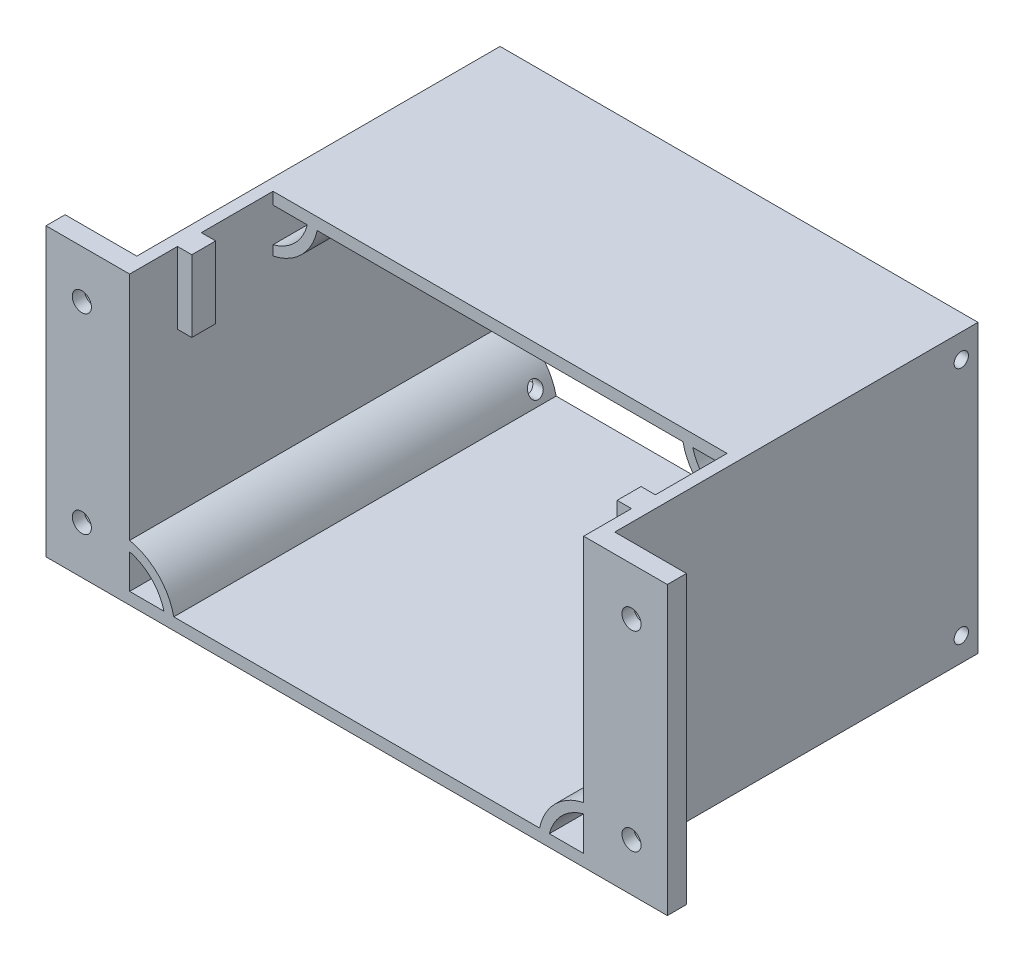
SolidWorks part; units mm, degrees
ref_plane "Front Plane" through (0, 0, 0) normal (0, 0, 1) x (1, 0, 0)
ref_plane "Top Plane" through (0, 0, 0) normal (0, 1, 0) x (1, 0, 0)
ref_plane "Right Plane" through (0, 0, 0) normal (1, 0, 0) x (0, 0, -1)
sketch "Sketch1" plane through (0, 0, 0) normal (0, 0, 1) x (1, 0, 0)
  line L1 (-40.2483, 30.9603) -> (59.7517, 30.9603)
  line L2 (-40.2483, 30.9603) -> (-40.2483, -29.0397)
  line L3 (-40.2483, -29.0397) -> (59.7517, -29.0397)
  line L4 (59.7517, 30.9603) -> (59.7517, -29.0397)
  line L5 (-37.7483, 28.4603) -> (57.2517, 28.4603)
  line L6 (-37.7483, 28.4603) -> (-37.7483, -26.5397)
  line L7 (-37.7483, -26.5397) -> (57.2517, -26.5397)
  line L8 (57.2517, 28.4603) -> (57.2517, -26.5397)
  arc A1 (-37.7483, 19.2236) -> (-28.5116, 28.4603) centre (-40.2483, 30.9603) ccw
  arc A2 (-37.7483, 21.2778) -> (-30.5659, 28.4603) centre (-40.2483, 30.9603) ccw
  arc A3 (48.015, 28.4603) -> (57.2517, 19.2236) centre (59.7517, 30.9603) ccw
  arc A4 (50.0692, 28.4603) -> (57.2517, 21.2778) centre (59.7517, 30.9603) ccw
  arc A5 (-28.5116, -26.5397) -> (-37.7483, -17.303) centre (-40.2483, -29.0397) ccw
  arc A6 (-30.5659, -26.5397) -> (-37.7483, -19.3573) centre (-40.2483, -29.0397) ccw
  arc A7 (57.2517, -17.303) -> (48.015, -26.5397) centre (59.7517, -29.0397) ccw
  arc A8 (57.2517, -19.3573) -> (50.0692, -26.5397) centre (59.7517, -29.0397) ccw
  dimension "D3" = 2.5
  dimension "D1" = 100
  dimension "D2" = 60
  dimension "D4" = 2.5
  dimension "D5" = 2.5
  dimension "D6" = 2.5
extrude "Boss-Extrude1" add sketch "Sketch1" along normal blind 150 contours L4 L1 L2 L3 L5 L8 L7 L6 | A2 L6 A1 L5 | A4 L5 A3 L8 | A8 L8 A7 L7 | A6 L7 A5 L6 region at (9.7517, 29.7941, 0) region at (-32.8375, 23.5494, 0) region at (52.3408, 23.5494, 0) region at (-32.8375, -21.6289, 0) region at (52.3408, -21.6289, 0)
sketch "Sketch2" plane through (0, 30.9603, 0) normal (0, 1, 0) x (1, 0, 0)
  line L1 (-37.7483, -150) -> (57.2517, -150)
  line L3 (-37.7483, -120) -> (57.2517, -120)
  line L6 (57.2517, -120) -> (-37.7483, -120)
  line L7 (57.2517, -120) -> (57.2517, -150)
  line L8 (57.2517, -150) -> (-37.7483, -150)
  line L9 (-37.7483, -120) -> (-37.7483, -150)
  line M4 (-40.2483, -150) -> (59.7517, -150)
  dimension "D1" = 30
  dimension "D2" = 95
extrude "Cut-Extrude1" cut sketch "Sketch2" against normal blind 20 contours L3 L9 L7 M4 region at (9.7517, 30.9603, 135)
sketch "Sketch3" plane through (0, 0, 0) normal (0, 0, -1) x (-1, 0, 0)
  line L1 (-62.7517, -32.0397) -> (43.2483, -32.0397)
  line L2 (-62.7517, -32.0397) -> (-62.7517, 33.9603)
  line L3 (-62.7517, 33.9603) -> (43.2483, 33.9603)
  line L4 (-59.7517, 30.9603) -> (-59.7517, -29.0397)
  line L5 (-59.7517, -29.0397) -> (40.2483, -29.0397)
  line L6 (40.2483, -29.0397) -> (40.2483, 30.9603)
  line L7 (40.2483, 30.9603) -> (-59.7517, 30.9603)
  line L8 (-59.7517, 30.9603) -> (-59.7517, -29.0397)
  line L9 (-59.7517, -29.0397) -> (40.2483, -29.0397)
  line L10 (40.2483, -29.0397) -> (40.2483, 30.9603)
  line L11 (40.2483, 30.9603) -> (-59.7517, 30.9603)
  line L12 (43.2483, -32.0397) -> (43.2483, 33.9603)
  dimension "D2" = 3
  dimension "D3" = 3
  dimension "D4" = 3
  dimension "D5" = 3
  dimension "D1" = 0
extrude "Boss-Extrude2" add sketch "Sketch3" along normal blind 13 and the other way blind 5
sketch "Sketch4" plane through (-43.2483, 0, 0) normal (-1, 0, 0) x (0, 0, 1)
  line L0 (5, 33.9603) -> (-13, 33.9603) construction
  circle A0 centre (-4, -24.0397) radius 1.5
  circle A1 centre (-4, 25.9603) radius 1.5
  dimension "D1" = 50
  dimension "D2" = 8
extrude "Cut-Extrude2" cut sketch "Sketch4" against normal blind 120
sketch "Sketch5" plane through (62.7517, 0, 0) normal (1, 0, 0) x (0, 0, -1)
  circle A0 centre (4, -24.0397) radius 3
  circle A1 centre (4, 25.9603) radius 3
extrude "Cut-Extrude3" cut sketch "Sketch5" against normal blind 1
sketch "Sketch6" plane through (-43.2483, 0, 0) normal (-1, 0, 0) x (0, 0, 1)
  circle A0 centre (-4, 25.9603) radius 3
  circle A1 centre (-4, -24.0877) radius 3
extrude "Cut-Extrude4" cut sketch "Sketch6" against normal blind 1
sketch "Sketch8" plane through (0, 0, -13) normal (0, 0, -1) x (-1, 0, 0)
  line L1 (-83.6072, 50.9392) -> (73.614, 50.9392)
  line L2 (-83.6072, 50.9392) -> (-83.6072, -48.614)
  line L3 (-83.6072, -48.614) -> (73.614, -48.614)
  line L4 (73.614, 50.9392) -> (73.614, -48.614)
extrude "Cut-Extrude6" cut sketch "Sketch8" against normal blind 83 contours L2 L3 L4 L1
sketch "Sketch9" plane through (59.7517, 0, 0) normal (1, 0, 0) x (0, 0, -1)
  circle A0 centre (-73.5, -24.0397) radius 1.5
  circle A1 centre (-73.5, 25.9603) radius 1.5
extrude "Cut-Extrude7" cut sketch "Sketch9" against normal blind 120
sketch "Sketch10" plane through (0, 30.9603, 0) normal (0, 1, 0) x (1, 0, 0)
  line L0 (-37.7483, -120) -> (-37.7483, -150) construction
  line L1 (-37.7483, -135) -> (-34.7483, -135)
  line L2 (-37.7483, -135) -> (-37.7483, -140)
  line L3 (-37.7483, -140) -> (-34.7483, -140)
  line L4 (-34.7483, -135) -> (-34.7483, -140)
  line L5 (57.2517, -120) -> (57.2517, -150) construction
  line L6 (54.2517, -135) -> (57.2517, -135)
  line L7 (54.2517, -135) -> (54.2517, -140)
  line L8 (54.2517, -140) -> (57.2517, -140)
  line L9 (57.2517, -135) -> (57.2517, -140)
  line L10 (57.2517, -140) -> (54.7517, -140) construction
extrude "Boss-Extrude3" add sketch "Sketch10" against normal blind 15
sketch "Sketch11" plane through (0, 0, 150) normal (0, 0, 1) x (1, 0, 0)
  line L10 (-40.2483, 30.9603) -> (-40.2483, -29.0397)
  line L12 (59.7517, 30.9603) -> (59.7517, -29.0397)
  line L17 (-40.2483, 30.9603) -> (-55.2483, 30.9603)
  line L18 (-40.2483, 30.9603) -> (-40.2483, -29.0397)
  line L19 (-40.2483, -29.0397) -> (-55.2483, -29.0397)
  line L20 (-55.2483, 30.9603) -> (-55.2483, -29.0397)
  line L21 (59.7517, 30.9603) -> (74.7517, 30.9603)
  line L22 (59.7517, 30.9603) -> (59.7517, -29.0397)
  line L23 (59.7517, -29.0397) -> (74.7517, -29.0397)
  line L24 (74.7517, 30.9603) -> (74.7517, -29.0397)
  circle A0 centre (-47.7483, 20.9603) radius 2
  circle A1 centre (-47.7483, -19.0397) radius 3
  circle A2 centre (67.2517, 20.9603) radius 3
  circle A4 centre (67.2517, -19.0397) radius 3
  circle A5 centre (-47.7483, 20.9603) radius 3
  circle A6 centre (67.2517, 20.9603) radius 2
  circle A7 centre (67.2517, -19.0397) radius 2
  circle A8 centre (-47.7483, -19.0397) radius 2
  point P8 (-47.7483, 30.9603)
  line M20 (-40.2483, 30.9603) -> (-40.2483, -29.0397)
  line M22 (59.7517, -29.0397) -> (59.7517, 30.9603)
  dimension "D1" = 15
  dimension "D2" = 15
  dimension "D3" = 40
  dimension "D4" = 10
  dimension "D5" = 7.5
  dimension "D6" = 7.5
  dimension "D7" = 40
  dimension "D8" = 10
extrude "Boss-Extrude4" add sketch "Sketch11" against normal blind 4 contours L17 L20 L19 A5 A1 M20 | L24 L21 L23 A4 A2 M22 region at (-47.7483, 0.9603, 150) region at (67.2517, 0.9603, 150)
extrude "Boss-Extrude5" add sketch "Sketch11<3>" against normal blind 2.5 contours A1 A8 | A5 A0 | A2 A6 | A4 A7 region at (-50.6635, -19.0397, 150) region at (64.3365, 20.9603, 150) region at (64.3365, -19.0397, 150) region at (-50.6635, 20.9603, 150)
sketch "Sketch11<3>" plane through (0, 0, 150) normal (0, 0, 1) x (1, 0, 0) same geometry as "Sketch11"
